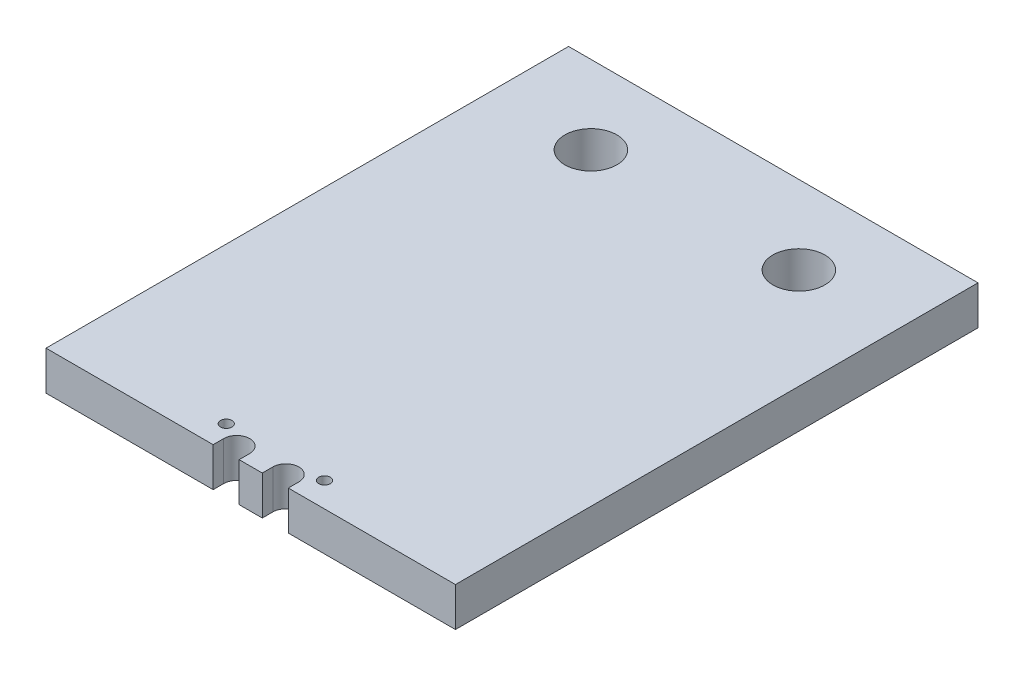
SolidWorks part; units mm, degrees
ref_plane "Front Plane" through (0, 0, 0) normal (0, 0, 1) x (1, 0, 0)
ref_plane "Top Plane" through (0, 0, 0) normal (0, 1, 0) x (1, 0, 0)
ref_plane "Right Plane" through (0, 0, 0) normal (1, 0, 0) x (0, 0, -1)
sketch "Sketch1" plane through (0, 0, 0) normal (0, 1, 0) x (1, 0, 0)
  line L0 (16, 1.1851) -> (36.4125, 1.1851)
  line L1 (16, 1.1851) -> (66, 1.1851) construction
  line L2 (16, 1.1851) -> (16, 65)
  line L3 (16, 65) -> (66, 65)
  line L4 (66, 1.1851) -> (66, 65)
  line L5 (66, 1.1851) -> (45.5875, 1.1851)
  line L6 (36.4125, 1.1851) -> (36.4125, 2.4762)
  line L7 (42.4125, 1.1851) -> (39.5875, 1.1851)
  line L8 (36.4125, 2.4762) -> (39.5875, 2.4762) construction
  line L9 (39.5875, 2.4762) -> (39.5875, 1.1851)
  line L10 (42.4125, 1.1851) -> (42.4125, 2.4762)
  line L11 (53.7, 55.4261) -> (28.3, 55.4261) construction
  line L12 (42.4125, 2.4762) -> (45.5875, 2.4762) construction
  line L13 (45.5875, 2.4762) -> (45.5875, 1.1851)
  line L15 (38, 4.0637) -> (44, 4.0637) construction
  line L23 (53.7, 55.4261) -> (66, 55.4261) construction
  line L27 (28.3, 55.4261) -> (16, 55.4261) construction
  arc A0 (36.4125, 2.4762) -> (39.5875, 2.4762) centre (38, 2.4762) cw
  arc A1 (42.4125, 2.4762) -> (45.5875, 2.4762) centre (44, 2.4762) cw
  circle A3 centre (35, 4.1973) radius 0.7
  circle A4 centre (53.7, 55.4261) radius 3.175
  circle A5 centre (28.3, 55.4261) radius 3.175
  circle A6 centre (47, 4.1973) radius 0.7
extrude "Boss-Extrude1" add sketch "Sketch1" against normal blind 4.7625
ref_axis "Axis1" through (35, -4.7625, -4.1973) along (0, 1, 0)
ref_axis "Axis2" through (47, -4.7625, -4.1973) along (0, 1, 0)
